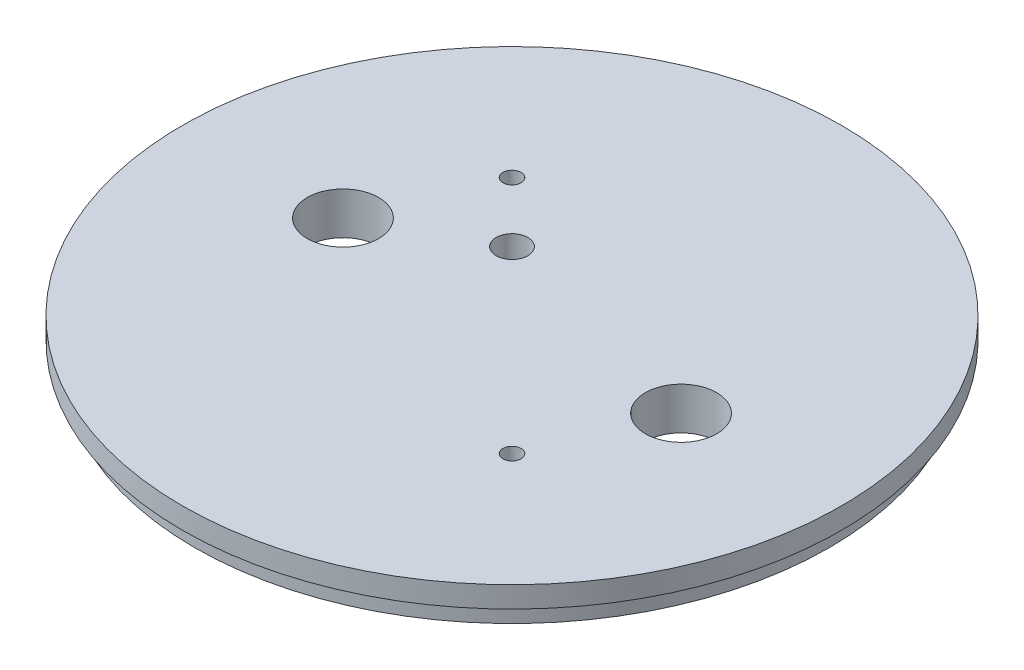
SolidWorks part; units mm, degrees
material "6061-T4 (SS)"
ref_plane "Front Plane" through (0, 0, 0) normal (0, 0, 1) x (1, 0, 0)
ref_plane "Top Plane" through (0, 0, 0) normal (0, 1, 0) x (1, 0, 0)
ref_plane "Right Plane" through (0, 0, 0) normal (1, 0, 0) x (0, 0, -1)
sketch "Sketch1" plane through (0, 0, 0) normal (0, 1, 0) x (1, 0, 0)
  line L0 (0, -49.5173) -> (0, 49.5173) construction
  line L1 (-49.5173, 0) -> (49.5173, 0) construction
  line L2 (-17.9605, 17.9605) -> (0, 0) construction
  line L3 (0, 56.7387) -> (0, 29.6936) construction
  line L4 (3.6407, 56.7387) -> (3.6407, 29.6936) construction
  line L5 (-3.6407, 56.7387) -> (-3.6407, 29.6936) construction
  line L6 (0, -56.7387) -> (0, -29.6936) construction
  line L7 (3.6407, -56.7387) -> (3.6407, -29.6936) construction
  line L8 (-3.6407, -56.7387) -> (-3.6407, -29.6936) construction
  line L9 (-35.014, -35.014) -> (54.3236, 54.3236) construction
  circle A0 centre (0, 0) radius 49.5173
  circle A1 centre (0, 0) radius 3.175 construction
  circle A2 centre (25.4, 0) radius 5.3578
  circle A3 centre (-25.4, 0) radius 5.3578
  circle A4 centre (-17.9605, 17.9605) radius 1.3589
  arc A6 (3.6407, 56.7387) -> (-3.6407, 56.7387) centre (0, 56.7387) ccw construction
  arc A7 (-3.6407, 29.6936) -> (3.6407, 29.6936) centre (0, 29.6936) ccw construction
  arc A8 (3.6407, -56.7387) -> (-3.6407, -56.7387) centre (0, -56.7387) cw construction
  arc A9 (-3.6407, -29.6936) -> (3.6407, -29.6936) centre (0, -29.6936) cw construction
  circle A10 centre (17.9605, -17.9605) radius 1.3589
  circle A11 centre (-8.9803, 8.9803) radius 2.3813
  circle A12 centre (8.9803, -8.9803) radius 2.3813 construction
  point P16 (0, 43.2162)
  point P19 (0, 0)
  point P26 (0, -43.2162)
  dimension "D1" = 99.0346
  dimension "D2" = 6.35
  dimension "D3" = 10.7156
  dimension "D5" = 2.7178
  dimension "D8" = 4.7625
  dimension "D6" = 25.4
  dimension "D7" = 45
  dimension "D4" = 45
  dimension "D9" = 25.4
extrude "Boss-Extrude1" add sketch "Sketch1" along normal blind 6.35
sketch "Sketch2" plane through (0, 0, 0) normal (0, -1, 0) x (1, 0, 0)
  circle A0 centre (0, 0) radius 49.5173
  circle A1 centre (0, 0) radius 47.6885
  dimension "D1" = 99.0346
  dimension "D2" = 95.377
extrude "Cut-Extrude1" cut sketch "Sketch2" against normal blind 3.175
sketch "Sketch3" plane through (0, 6.35, 0) normal (0, 1, 0) x (1, 0, 0)
  line L0 (0, 49.5173) -> (0, -49.5173) construction
  line L1 (-49.5173, 0) -> (49.5173, 0) construction
  line L2 (0, 34.925) -> (0, 13.335) construction
  line L3 (3.2385, 34.925) -> (3.2385, 13.335)
  line L4 (-3.2385, 34.925) -> (-3.2385, 13.335)
  line L5 (0, -34.925) -> (0, -13.335) construction
  line L6 (3.2385, -34.925) -> (3.2385, -13.335)
  line L7 (-3.2385, -34.925) -> (-3.2385, -13.335)
  circle A0 centre (0, 0) radius 49.5173 construction
  arc A1 (3.2385, 34.925) -> (-3.2385, 34.925) centre (0, 34.925) ccw
  arc A2 (-3.2385, 13.335) -> (3.2385, 13.335) centre (0, 13.335) ccw
  arc A3 (3.2385, -34.925) -> (-3.2385, -34.925) centre (0, -34.925) cw
  arc A4 (-3.2385, -13.335) -> (3.2385, -13.335) centre (0, -13.335) cw
  point P7 (0, 13.335)
  point P8 (0, 34.925)
  point P12 (0, 24.13)
  point P20 (0, -24.13)
  point P25 (0, -34.925)
  point P26 (0, -13.335)
  dimension "D1" = 13.335
  dimension "D2" = 34.925
  dimension "D3" = 6.477
extrude "Cut-Extrude2" cut sketch "Sketch3" against normal blind 3.81 from offset 2.794 offset against normal yes
equation "\"Coupler_OD\" = 3.899in"
equation "\"Coupler_ID\" = 3.755in"
equation "\"Lead_Screw_Hole_Diam\" = (27/64)*1in"
equation "\"Lead_Screw_Dist\" = 2in"
equation "\"D9@Sketch1\"=\"Lead_Screw_Dist\"/2"
equation "\"D3@Sketch1\"=\"Lead_Screw_Hole_Diam\""
equation "\"Body_Tube_OD\"= 4.024in"
equation "\"Body_Tube_ID\"= 3.90in"
equation "\"Avionics_Bulkhead_Thickness\" = 0.25in"
equation "\"Avionics_Bulkhead_Lip\" = 0.125in"
equation "\"Lead_Screw_Diam\" = 0.375in"
equation "\"D1@Sketch2\"=\"Coupler_OD\""
equation "\"D2@Sketch2\"=\"Coupler_ID\""
equation "\"D1@Sketch1\"=\"Coupler_OD\""
equation "\"D1@Boss-Extrude1\"=\"Avionics_Bulkhead_Thickness\""
equation "\"D1@Cut-Extrude1\"=\"Avionics_Bulkhead_Lip\""
